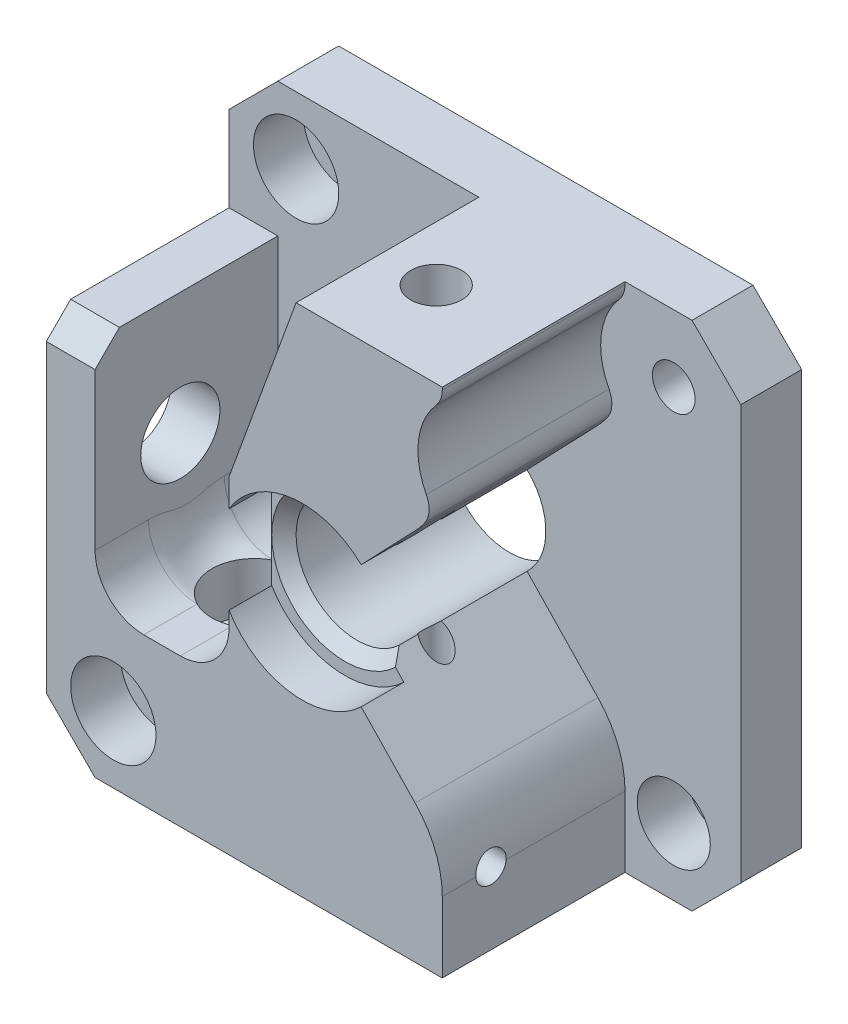
SolidWorks part; units mm, degrees
material "6063-T1"
ref_plane "Piano frontale" through (0, 0, 0) normal (0, 0, 1) x (1, 0, 0)
ref_plane "Piano superiore" through (0, 0, 0) normal (0, 1, 0) x (1, 0, 0)
ref_plane "Piano destro" through (0, 0, 0) normal (1, 0, 0) x (0, 0, -1)
ref_plane "Motor plane" through (0, 0, -20) normal (0, 0, 1) x (1, 0, 0)
sketch "Schizzo1" plane through (0, 0, -20) normal (0, 0, 1) x (1, 0, 0)
  line L1 (15.5, -15.5) -> (-15.5, -15.5) construction
  line L2 (15.5, -15.5) -> (15.5, 15.5) construction
  line L3 (15.5, 15.5) -> (-15.5, 15.5) construction
  line L4 (-15.5, -15.5) -> (-15.5, 15.5) construction
  line L5 (15.5, -15.5) -> (-15.5, 15.5) construction
  line L6 (15.5, 15.5) -> (-15.5, -15.5) construction
  line L7 (21, -21) -> (-21, -21)
  line L8 (21, -21) -> (21, 21)
  line L9 (21, 21) -> (-21, 21)
  line L10 (-21, -21) -> (-21, 21)
  line L11 (21, -21) -> (-21, 21) construction
  line L12 (21, 21) -> (-21, -21) construction
  circle A0 centre (-15.5, 15.5) radius 1.75
  circle A1 centre (15.5, 15.5) radius 1.75
  circle A2 centre (-15.5, -15.5) radius 1.75
  circle A3 centre (15.5, -15.5) radius 1.75
  dimension "D3" = 3.5
  dimension "D1" = 31
  dimension "D2" = 31
  dimension "D5" = 42
  dimension "D6" = 42
extrude "Estrusione-Estrusione1" add sketch "Schizzo1" along normal blind 5
sketch "Schizzo3" plane through (0, 0, -15) normal (0, 0, 1) x (1, 0, 0)
  line L0 (-21, -21) -> (21, -21) construction
  line L1 (11.5, -21) -> (-6, -21)
  line L2 (11.5, -21) -> (11.5, 21)
  line L3 (11.5, 21) -> (-6, 21)
  line L4 (-6, -21) -> (-6, 21)
  line L5 (21, 21) -> (-21, 21) construction
  line L6 (-21, 21) -> (-21, -21) construction
  line L7 (21, -21) -> (21, 21) construction
  dimension "D1" = 15
  dimension "D2" = 9.5
extrude "Estrusione-Estrusione4" add sketch "Schizzo3" along normal blind 15
sketch "Schizzo4" plane through (0, 0, 0) normal (0, 0, 1) x (1, 0, 0)
  circle A0 centre (0, 0) radius 5
  dimension "D1" = 10
extrude "Taglio-Estrusione1" cut sketch "Schizzo4" against normal through all
ref_plane "Piano3" through (4, 0, 0) normal (1, 0, 0) x (0, 0, -1)
sketch "Schizzo6" plane through (0, -21, 0) normal (0, -1, 0) x (1, 0, 0)
  line L0 (11.5, -7) -> (-6, -7) construction
  line L2 (-6, 0) -> (-6, -15) construction
  line L3 (4, -11) -> (4, 11) construction
  line L4 (4, -2.5823) -> (4, -27.3722) construction
  line L9 (23.1, -20) -> (-23.1, -20) construction
  circle A0 centre (4, -7) radius 1.1
  point P10 (4, -7)
  dimension "D1" = 2.2
  dimension "D2" = 13
extrude "Taglio-Estrusione3" cut sketch "Schizzo6" against normal through all
sketch "Schizzo7" plane through (0, 0, 0) normal (0, 0, 1) x (1, 0, 0)
  line L0 (11.5, 0) -> (-6, 0) construction
  line L1 (11.5, -21) -> (11.5, 21) construction
  line L2 (-6, 21) -> (-6, -21) construction
  line L3 (11.5, 12) -> (0, 0)
  line L4 (11.5, 12) -> (11.5, -12)
  line L5 (11.5, -12) -> (0, 0)
  dimension "D1" = 12
extrude "Taglio-Estrusione4" cut sketch "Schizzo7" against normal blind 15
fillet "Raccordo2" radius 8 1 edges at (11.5, 12, -7.5)
fillet "Raccordo3" radius 8 1 edges at (11.5, -12, -7.5)
chamfer "Smusso1" distance 4 angle 45 4 edges at (21, -21, -17.5) (-21, -21, -17.5) (-21, 21, -17.5) (21, 21, -17.5)
sketch "Schizzo22" plane through (11.5, 0, 0) normal (1, 0, 0) x (0, 0, -1)
  line L0 (15, -17) -> (15, 17) construction
  point P0 (4, -15.1119)
  dimension "D1" = 11
hole_wizard "Foro filettato M3-2" positions "Schizzo24" profile "Schizzo23" tap size "M3" standard "ISO"
sketch "Schizzo24" plane through (11.5, 0, 0) normal (1, 0, 0) x (0, 0, -1)
  point P0 (4, -15.1119)
sketch "Schizzo23" plane through (11.5, -15.1119, -4) normal (0, 1, 0) x (0, 0, -1)
  line L0 (0, 0) -> (0, 12.7511)
  line L1 (0, 12.7511) -> (1.25, 12)
  line L2 (1.25, 12) -> (1.25, 0)
  line L5 (1.25, 0) -> (0, 0)
  line L10 (0, 12.7511) -> (-1.25, 12) construction
  line L11 (0, -6.35) -> (0, 107.95) construction
  dimension "Tap Drill Dia." = 2.5
  dimension "Tap Drill Depth" = 12
  dimension "Drill Angle" = 118
cosmetic thread "Filettatura del foro2" parameters "D1"=6, "D2"=3
sketch "Schizzo28" plane through (0, 0, -15) normal (0, 0, 1) x (1, 0, 0)
  line L1 (-21, 0) -> (21, 0) construction
  line L2 (-21, 17) -> (-21, -17) construction
  line L3 (21, -17) -> (21, 17) construction
  line L4 (-21, -10) -> (-21, 10)
  line L6 (-21, 10) -> (-17, 10)
  line L7 (-17, 10) -> (-17, -10)
  line L8 (-21, -10) -> (-17, -10)
  point P13 (-17, 0)
  dimension "D1" = 4
  dimension "D2" = 10
extrude "Estrusione-Estrusione5" add sketch "Schizzo28" along normal blind 15
sketch "Schizzo29" plane through (0, 0, -15) normal (0, 0, 1) x (1, 0, 0)
  circle A0 centre (-15.5, 15.5) radius 3.5
  circle A2 centre (15.5, -15.5) radius 3
  dimension "D1" = 7
extrude "Taglio-Estrusione6" cut sketch "Schizzo29" against normal blind 4.1
chamfer "Smusso3" distance 5.5 angle 70 1 edges first distance on face at (5.1, 21, -7)
sketch "Schizzo30" plane through (-21, 0, 0) normal (-1, 0, 0) x (0, 0, 1)
  line L0 (0, 0) -> (-20, 0) construction
  line L1 (0, 10) -> (0, -10) construction
  line L2 (-20, -23.1) -> (-20, 23.1) construction
  circle A0 centre (-7, 0) radius 3.25
  dimension "D1" = 6.5
  dimension "D2" = 7
extrude "Taglio-Estrusione7" cut sketch "Schizzo30" against normal blind 4
chamfer "Smusso4" distance 2 angle 45 1 edges at (-19, 10, 0)
hole_wizard "Foro filettato M5-1" positions "Schizzo3D1" profile "Schizzo31" tap size "M5" standard "ISO"
sketch3d "Schizzo3D1"
  line L0 (4, 21, -7) -> (4, 3.6099, -7) construction
  point P0 (4, 21, -7)
sketch "Schizzo31" plane through (4, 21, -7) normal (1, 0, 0) x (0, 0, 1)
  line L0 (0, 0) -> (0, 6.2618)
  line L1 (0, 6.2618) -> (2.1, 5)
  line L2 (2.1, 5) -> (2.1, 0)
  line L5 (2.1, 0) -> (0, 0)
  line L10 (0, 6.2618) -> (-2.1, 5) construction
  line L11 (0, -6.35) -> (0, 107.95) construction
  dimension "Tap Drill Dia." = 4.2
  dimension "Tap Drill Depth" = 5
  dimension "Drill Angle" = 118
cosmetic thread "Filettatura del foro3" parameters "D1"=5, "D2"=5
sketch "Schizzo32" plane through (0, 0, 0) normal (0, 0, 1) x (1, 0, 0)
  circle A0 centre (0, 0) radius 7
  dimension "D1" = 14
extrude "Taglio-Estrusione8" cut sketch "Schizzo32" against normal blind 3.5
sketch "Schizzo33" plane through (0, 0, -20) normal (0, 0, -1) x (-1, 0, 0)
  circle A0 centre (0, 0) radius 12
  dimension "D1" = 24
extrude "Taglio-Estrusione9" cut sketch "Schizzo33" against normal blind 3
sketch "Schizzo34" plane through (0, 0, 0) normal (0, 0, 1) x (1, 0, 0)
  circle A0 centre (15.5, 15.5) radius 6
  dimension "D1" = 12
extrude "Taglio-Estrusione10" cut sketch "Schizzo34" along direction (0, 0, 1) on the side against the normal blind 15
fillet "Raccordo4" radius 2 1 edges at (11.5, 19.9721, -7.5)
fillet "Raccordo5" radius 2 1 edges at (10.7505, 11.8336, -7.5)
chamfer "Smusso5" distance 1 angle 45 1 edges at (-5, 0, -3.5)
sketch "Schizzo35" plane through (0, 0, -15) normal (0, 0, 1) x (1, 0, 0)
  line L0 (-17, -8.8557) -> (-6, -8.8557)
  line L1 (-17, -10) -> (-17, 10) construction
  line L3 (-6, -8.8557) -> (-6, -21)
  line L4 (-6, -21) -> (-17, -21)
  line L5 (-17, -21) -> (-21, -17)
  line L6 (-21, -17) -> (-21, -10)
  line L7 (-21, -10) -> (-17, -10)
  line L8 (-17, -10) -> (-17, -8.8557)
  line L9 (-6, 5.8889) -> (-6, -21) construction
extrude "Estrusione-Estrusione6" add sketch "Schizzo35" along normal up to vertex (15 mm away) up to point (-6, -3.6056, 0)
sketch "Schizzo36" plane through (0, 0, 0) normal (0, 0, 1) x (1, 0, 0)
  circle A0 centre (-15.5, -15.5) radius 1.75
extrude "Taglio-Estrusione11" cut sketch "Schizzo36" against normal through all
sketch "Schizzo37" plane through (0, -8.8557, 0) normal (0, 1, 0) x (1, 0, 0)
  line L0 (-17, 7.5) -> (-5.8125, 7.5) construction
  line L1 (-17, 0) -> (-17, 15) construction
  line L2 (-11.4063, 7.5) -> (-11.4063, 0) construction
  line L3 (-6, 0) -> (-17, 0) construction
  circle A0 centre (-11.4063, 7.5) radius 2.1
  dimension "D1" = 4.2
extrude "Taglio-Estrusione12" cut sketch "Schizzo37" against normal through all
sketch "Schizzo38" plane through (0, 0, 0) normal (0, 0, 1) x (1, 0, 0)
  circle A0 centre (-15.5, -15.5) radius 3.5
  dimension "D1" = 7
extrude "Taglio-Estrusione13" cut sketch "Schizzo38" against normal blind 4.1
sketch "Schizzo39" plane through (0, -8.8557, 0) normal (0, 1, 0) x (1, 0, 0)
  circle A0 centre (-11.4063, 7.5) radius 3.5
  dimension "D1" = 7
extrude "Taglio-Estrusione14" cut sketch "Schizzo39" against normal blind 4.1
fillet "Raccordo6" radius 4 2 edges at (-6, -8.8557, -7.5) (-17, -8.8557, -7.5)
sketch "Schizzo40" plane through (0, -21, 0) normal (0, -1, 0) x (1, 0, 0)
  line L0 (4, -11) -> (4, 11) construction
  line L1 (23.1, -20) -> (-23.1, -20) construction
  circle A0 centre (4, -15) radius 1
  circle A1 centre (4, -7) radius 1.1 construction
  dimension "D1" = 2
  dimension "D3" = 8
  dimension "D2" = 5
extrude "Taglio-Estrusione15" cut sketch "Schizzo40" against normal blind 6
